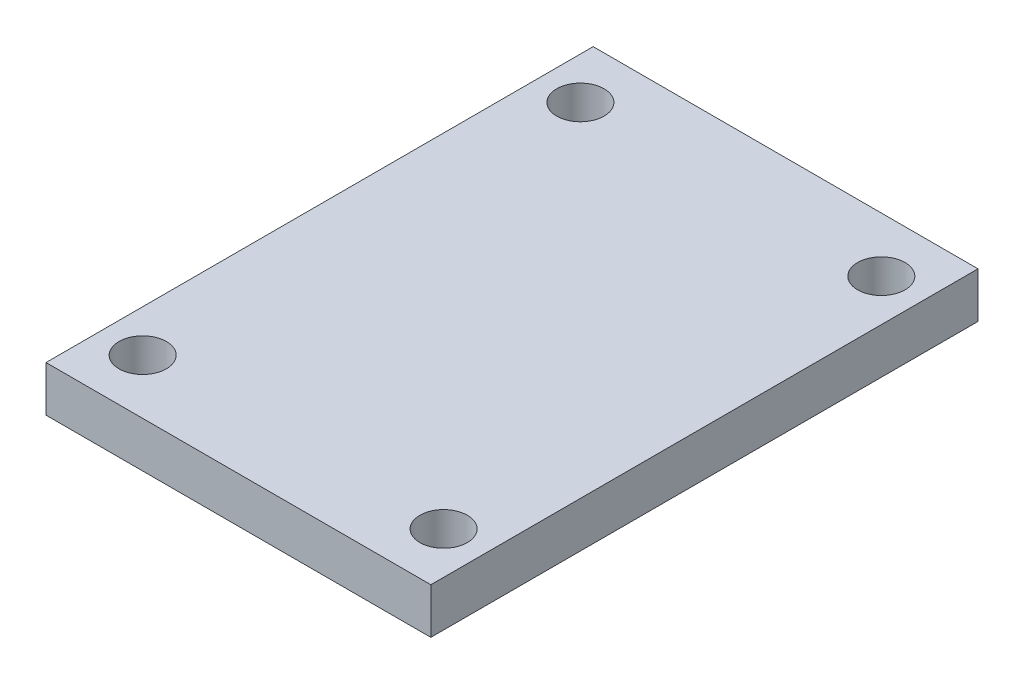
SolidWorks part; units mm, degrees
ref_plane "Front Plane" through (0, 0, 0) normal (0, 0, 1) x (1, 0, 0)
ref_plane "Top Plane" through (0, 0, 0) normal (0, 1, 0) x (1, 0, 0)
ref_plane "Right Plane" through (0, 0, 0) normal (1, 0, 0) x (0, 0, -1)
sketch "Sketch1" plane through (0, 0, 0) normal (0, 1, 0) x (1, 0, 0)
  line L1 (0, 0) -> (-54.61, 0)
  line L2 (0, 0) -> (0, 76.2)
  line L3 (0, 76.2) -> (-54.61, 76.2)
  line L4 (-54.61, 0) -> (-54.61, 76.2)
  dimension "D1" = 76.2
  dimension "D2" = 54.61
extrude "Boss-Extrude1" add sketch "Sketch1" along normal blind 6.35
sketch "Sketch2" plane through (0, 6.35, 0) normal (0, 1, 0) x (1, 0, 0)
  line L0 (0, 0) -> (0, 76.2) construction
  line L1 (-54.61, 0) -> (0, 0) construction
  circle A0 centre (-6.35, 7.62) radius 3.302
  circle A4 centre (-6.35, 68.58) radius 3.302
  point P6 (0, 0)
  point P7 (0, 0)
  point P14 (0, 0)
  point P15 (0, 0)
  dimension "D2" = 6.604
  dimension "D1" = 6.35
  dimension "D3" = 7.62
  dimension "D4" = 68.58
extrude "Cut-Extrude1" cut sketch "Sketch2" against normal through all
ref_plane "KORAL!!!" through (-27.305, 0, 0) normal (1, 0, 0) x (0, 0, -1)
mirror "Mirror1" about plane through (-27.305, 0, 0) normal (1, 0, 0) of "Cut-Extrude1"
sketch "Sketch3" plane through (0, 6.35, 0) normal (0, 1, 0) x (1, 0, 0)
  line L0 (0, 0) -> (-0.508, 0)
  line L1 (-54.61, 0) -> (0, 0) construction
  line L2 (-0.508, 0) -> (-0.508, 76.2)
  line L3 (0, 76.2) -> (-54.61, 76.2) construction
  line L4 (-0.508, 76.2) -> (0, 76.2)
  line L5 (0, 76.2) -> (0, 0)
  dimension "D1" = 0.508
extrude "Cut-Extrude2" cut sketch "Sketch3" against normal through all
mirror "Mirror2" about plane through (-27.305, 0, 0) normal (1, 0, 0) of "Cut-Extrude2"
